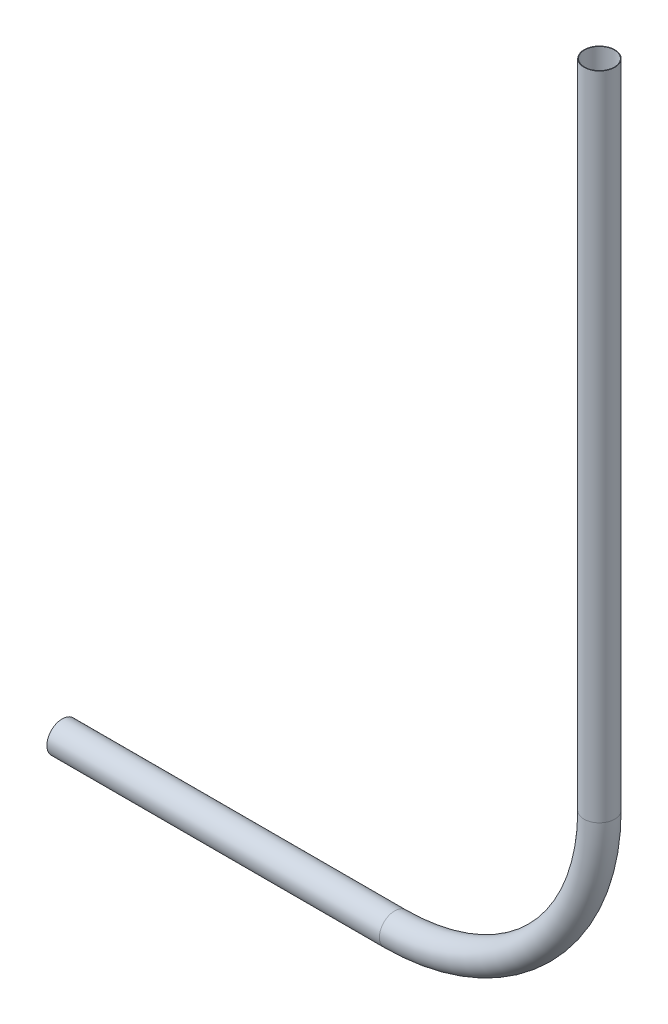
SolidWorks part; units mm, degrees
ref_plane "Front Plane" through (0, 0, 0) normal (0, 0, 1) x (1, 0, 0)
ref_plane "Top Plane" through (0, 0, 0) normal (0, 1, 0) x (1, 0, 0)
ref_plane "Right Plane" through (0, 0, 0) normal (1, 0, 0) x (0, 0, -1)
sketch3d "3DSketch1"
  line L0 (-23035.2769, -7934.1096, 40217.8019) -> (-22963.5408, -7934.1096, 40217.8019) construction
  line L1 (-22963.5408, -7934.1096, 40217.8019) -> (-22313.789, -7934.1096, 40217.8019)
  line L2 (-21913.789, -7534.1096, 40217.8019) -> (-21913.789, -6261.8104, 40217.8019)
  line L3 (-21632.6177, -6261.8104, 40486.7002) -> (-21913.789, -6261.8104, 40486.7002) construction
  line L4 (-21913.789, -6261.8104, 40217.8019) -> (-21913.789, -6261.8104, 40486.7002) construction
  circle A0 centre (-23035.2769, -7934.1096, 40217.8019) radius 26.2509 construction
  arc A1 (-21913.789, -7534.1096, 40217.8019) -> (-22313.789, -7934.1096, 40217.8019) centre (-22313.789, -7534.1096, 40217.8019) ccw
  circle A2 centre (-21632.6177, -6261.8104, 40486.7002) radius 30 construction
  point P4 (-23009.026, -7934.1096, 40217.8019)
  point P9 (-21913.789, -7934.1096, 40217.8019)
  point P10 (-22313.789, -7534.1096, 39817.8019)
  point P21 (-21632.6177, -6231.8104, 40486.7002)
  dimension "D1" = 400
sweep "Sweep-Thin1" add path "3DSketch1" circular profile diameter 60 parameters "D1"=1, "D3"=60
